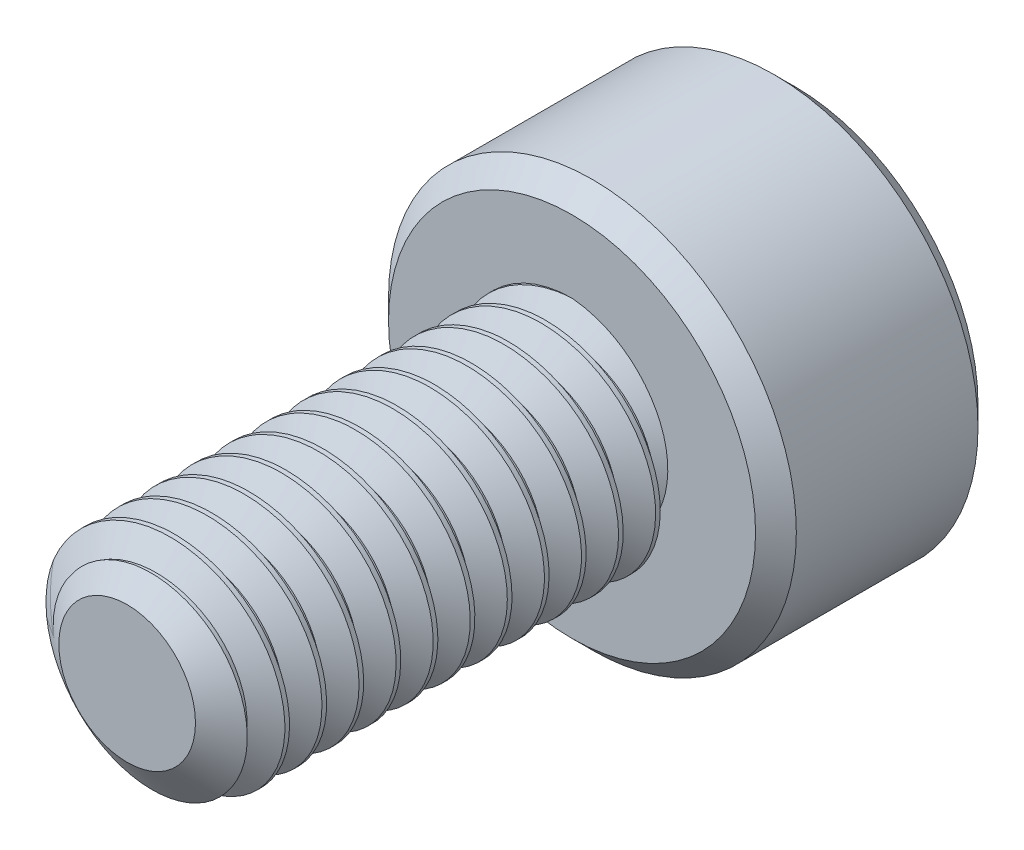
SolidWorks part; units mm, degrees
other "DetailItem1"
ref_plane "Front Plane" through (0, 0, 0) normal (0, 0, 1) x (1, 0, 0)
ref_plane "Top Plane" through (0, 0, 0) normal (0, 1, 0) x (1, 0, 0)
ref_plane "Right Plane" through (0, 0, 0) normal (1, 0, 0) x (0, 0, -1)
sketch "Sketch1" plane through (0, 0, 0) normal (0, 0, 1) x (1, 0, 0)
  circle A0 centre (0, 0) radius 1.5
  dimension "OD" = 3
extrude "Extrude1" add sketch "Sketch1" against normal blind 6
sketch "Sketch2" plane through (0, 0, 0) normal (0, 0, 1) x (1, 0, 0)
  circle A0 centre (0, 0) radius 1.5 construction
  circle A1 centre (0, 0) radius 1.5
curve "Helix/Spiral1" pitch 0.5 height 6.5 radius 1.5 centre (0, 0, 0) axis (0, 0, -1) start towards (0, 1, 0) parameters "pitch"=0.5
sketch "Sketch3" plane through (0, 0, 0) normal (1, 0, 0) x (0, 0, -1)
  line L0 (-0.4375, 1.5) -> (-0.25, 1.1752)
  line L1 (-0.25, 1.1752) -> (-0.1875, 1.1752)
  line L2 (-0.1875, 1.1752) -> (0, 1.5)
  line L3 (-0.4375, 1.5) -> (0, 1.5)
  line L4 (-0.2187, 1.5) -> (-0.2188, 1.1752) construction
  line L5 (-0.3438, 1.3376) -> (-0.0938, 1.3376) construction
  line L6 (0, 1.5) -> (0, -1.5) construction
  dimension "D1" = 0.0625
  dimension "D2" = 0.25
  dimension "D3" = 60
sweep "Cut-Sweep1" cut profiles "Sketch3" path "Helix/Spiral1"
sketch "Sketch4" plane through (0, 0, 0) normal (1, 0, 0) x (0, 0, -1)
  line L0 (0.4053, 1.5) -> (0, 0.9212)
  line L1 (0, 0.9212) -> (0, 1.5)
  line L2 (0.4053, 1.5) -> (0, 1.5)
  line L3 (-0.4375, 1.5) -> (0, 1.5) construction
  line L4 (0, 0) -> (7.0209, 0) construction
  dimension "D1" = 55
  dimension "D2" = 0.254
revolve "Cut-Revolve1" cut sketch "Sketch4" angle 360 about L4
sketch "Sketch6" plane through (0, 0, -6) normal (0, 0, -1) x (-1, 0, 0)
  circle A0 centre (0, 0) radius 2.75
  dimension "head dia" = 5.5
extrude "Extrude2" add sketch "Sketch6" along normal blind 3
sketch "Sketch7" plane through (0, 0, -9) normal (0, 0, -1) x (-1, 0, 0)
  line L1 (0, 1.4434) -> (-1.25, 0.7217)
  line L2 (-1.25, 0.7217) -> (-1.25, -0.7217)
  line L3 (-1.25, -0.7217) -> (0, -1.4434)
  line L4 (0, -1.4434) -> (1.25, -0.7217)
  line L5 (1.25, -0.7217) -> (1.25, 0.7217)
  line L6 (1.25, 0.7217) -> (0, 1.4434)
  circle A0 centre (0, 0) radius 1.25 construction
  dimension "hex dia" = 2.5
extrude "Cut-Extrude1" cut sketch "Sketch7" against normal blind 1.875
sketch "Sketch8" plane through (0, 0, -9) normal (0, 0, -1) x (-1, 0, 0)
  circle A0 centre (0, 0) radius 1.4434
extrude "Cut-Extrude2" cut sketch "Sketch8" against normal through all draft 45
chamfer "Chamfer1" distance 0.275 angle 45 2 edges at (-2.75, 0, -9) (-2.75, 0, -6)
sketch "Sketch10" plane through (0, 0, -6) normal (0, 0, 1) x (1, 0, 0)
  circle A1 centre (0, 0) radius 1.5
  circle A2 centre (0, 0) radius 1.5
  dimension "D1" = 0
ref_plane "Plane1" through (0, 0, 0) normal (0, 0, 1) x (1, 0, 0)
extrude "partial thread" [suppressed] add sketch "Sketch10" along normal up to surface (4 mm away) separate body up to plane "Plane1"
chamfer "Chamfer2" [suppressed] distance 0.06 angle 45
combine bodies "Combine1" [suppressed] operation type add bodies to combine 107 108
sketch "Sketch9" plane through (0, 0, 0) normal (1, 0, 0) x (0, 0, -1)
  line L0 (0, 1.5) -> (0, -1.5) construction
  line L1 (1.25, 1.5) -> (1.25, -1.5) construction
  dimension "D1" = 1.25
equation "\"D3@Helix/Spiral1\" = \"screw length@Extrude1\"+\"pitch@Helix/Spiral1\""
equation "\"D1@Sketch3\" = \"pitch@Helix/Spiral1\"*.125"
equation "\"D2@Sketch3\" = \"pitch@Helix/Spiral1\"*.5"
equation "\"D1@Cut-Extrude1\" = \"hex dia@Sketch7\"*.75"
equation "\"D1@Chamfer1\" = \"head dia@Sketch6\"*.05"
equation "\"D1@Sketch9\" = \"pitch@Helix/Spiral1\"*2.5"
equation "\"D1@Chamfer2\"=\"OD@Sketch1\"*.02"
